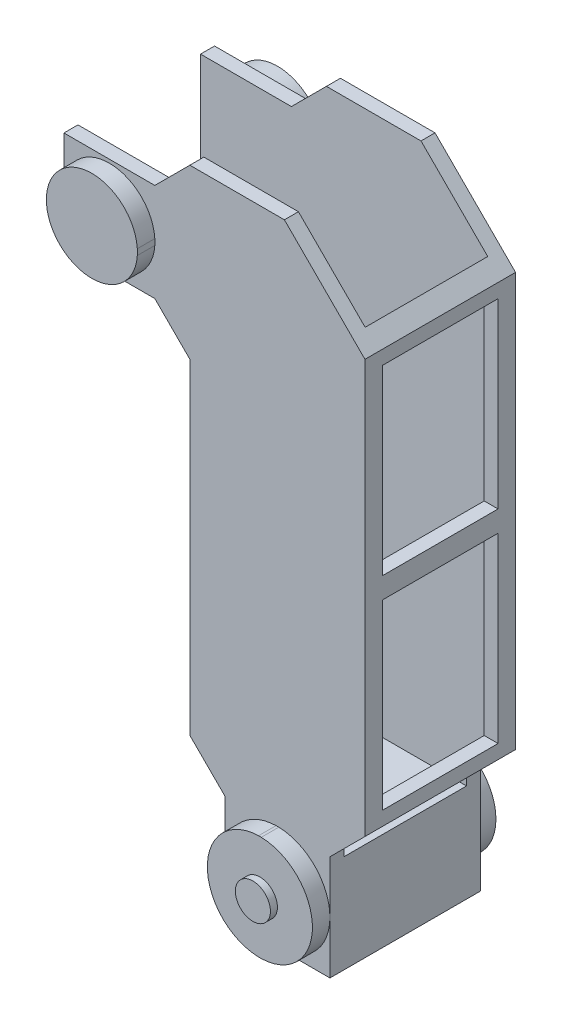
SolidWorks part; units mm, degrees
ref_plane "Front Plane" through (0, 0, 0) normal (0, 0, 1) x (1, 0, 0)
ref_plane "Top Plane" through (0, 0, 0) normal (0, 1, 0) x (1, 0, 0)
ref_plane "Right Plane" through (0, 0, 0) normal (1, 0, 0) x (0, 0, -1)
sketch "Sketch1" plane through (0, 0, 0) normal (0, 0, 1) x (1, 0, 0)
  line L0 (-42.9449, 80.5) -> (-16.9666, 80.5)
  line L1 (-7, 90.5) -> (20, 90.5)
  line L2 (-42.9449, 80.5) -> (-42.9449, 52.5)
  line L3 (3, -90.48) -> (33, -90.48)
  line L4 (43, 67.5) -> (43, -50.5)
  line L5 (-38.2486, 80.5) -> (43, -90.5) construction
  line L6 (-43, -90.5) -> (43, 90.5) construction
  line L7 (-7, 90.5) -> (-17, 80.5)
  line L8 (20, 90.5) -> (43, 67.5)
  line L11 (-7, 42.52) -> (-7, -50.48)
  line L14 (3, -90.48) -> (3, -60.48)
  line L15 (33, -90.48) -> (33, -60.5)
  line L17 (43, -50.5) -> (33, -60.5)
  line L18 (-7, -50.48) -> (3, -60.48)
  line L23 (-42.9449, 52.52) -> (-42.9449, 52.5)
  line L24 (-17, 52.52) -> (-42.9449, 52.52)
  line L26 (-7, 42.52) -> (-17, 52.52)
  circle A0 centre (17.8984, -75.5) radius 14.5
  circle A1 centre (-29.9725, 66.5) radius 13
  point P0 (0, 0)
  point P6 (-42.9449, 80.5)
  point P7 (-42.9449, 66.5)
  point P9 (43, 67.5)
  point P10 (20, 90.5)
  point P11 (-7, 90.5)
  point P14 (-17, 80.5)
  point P19 (-42.9449, 68.3358)
  point P25 (-7, -50.48)
  point P33 (43, -50.5)
  point P35 (3, -90.48)
  point P36 (33, -90.48)
  point P55 (-7, 42.52)
extrude "Boss-Extrude1" add sketch "Sketch1" along normal blind 43 contours A1 L2 L24 L26 L11 L18 L14 L3 L15 L17 L4 L8 L1 L7 L0 A0 region at (14.8624, 14.6618, 0)
extrude "Boss-Extrude2" add sketch "Sketch1<5>" along normal blind 43 contours A0 region at (17.8984, -75.5, 0)
sketch "Sketch1<5>" plane through (0, 0, 0) normal (0, 0, 1) x (1, 0, 0) same geometry as "Sketch1"
extrude "Boss-Extrude3" add sketch "Sketch1<6>" along normal blind 43 contours L2 A1 region at (-29.9717, 66.5, 0)
sketch "Sketch1<6>" plane through (0, 0, 0) normal (0, 0, 1) x (1, 0, 0) same geometry as "Sketch1"
extrude "Boss-Extrude4" add sketch "Sketch1<7>" against normal blind 5 contours L2 A1 region at (-29.9717, 66.5, 0)
sketch "Sketch1<7>" plane through (0, 0, 0) normal (0, 0, 1) x (1, 0, 0) same geometry as "Sketch1"
extrude "Boss-Extrude5" add sketch "Sketch1<8>" against normal blind 5 contours A0 region at (17.8984, -75.5, 0)
sketch "Sketch1<8>" plane through (0, 0, 0) normal (0, 0, 1) x (1, 0, 0) same geometry as "Sketch1"
sketch "Sketch3" plane through (0, 0, -5) normal (0, 0, -1) x (-1, 0, 0)
  circle A0 centre (-17.8984, -75.5) radius 5
  point P0 (-17.8984, -75.5)
extrude "Boss-Extrude6" add sketch "Sketch3" along normal blind 2
sketch "Sketch4" plane through (0, 0, 43) normal (0, 0, 1) x (1, 0, 0)
  line L0 (-17, 80.5) -> (-17, 52.52)
  line L1 (-17, 66.51) -> (-42.9449, 66.51)
  line L2 (-42.9449, 80.5) -> (-42.9449, 52.52) construction
  line L3 (3, -60.48) -> (33, -60.5)
  line L4 (18, -60.49) -> (18, -90.48)
  line L5 (3, -90.48) -> (33, -90.48) construction
  circle A0 centre (-29.9725, 66.51) radius 13
  circle A1 centre (18, -75.485) radius 15
  point P8 (-29.9725, 66.51)
  point P19 (18, -75.485)
  line M3 (-42.9449, 80.5) -> (-42.9449, 52.52)
  line M9 (3, -90.48) -> (33, -90.48)
extrude "Boss-Extrude7" add sketch "Sketch4" along normal blind 5 contours L0 A0 L1 M3 | A0 L0 L1 M3 region at (-29.9725, 72.028, 43) region at (-29.9725, 60.992, 43)
extrude "Boss-Extrude8" add sketch "Sketch4<3>" along normal blind 5 contours L3 A1 L4 M9 | A1 L3 L4 M9 region at (11.6338, -75.485, 43) region at (24.3662, -75.485, 43)
sketch "Sketch4<3>" plane through (0, 0, 43) normal (0, 0, 1) x (1, 0, 0) same geometry as "Sketch4"
sketch "Sketch5" plane through (0, 0, 48) normal (0, 0, 1) x (1, 0, 0)
  circle A0 centre (18, -75.485) radius 5
extrude "Boss-Extrude9" add sketch "Sketch5" along normal blind 2
sketch "Sketch6" plane through (-42.9449, 0, 0) normal (-1, 0, 0) x (0, 0, 1)
  line L0 (43, 80.5) -> (0, 80.5) construction
  line L1 (21.5, 80.5) -> (21.5, 52.52)
  line L2 (43, 52.52) -> (0, 52.52) construction
  line L4 (4, 80.51) -> (39, 80.51)
  line L5 (4, 80.51) -> (4, 52.51)
  line L6 (4, 52.51) -> (39, 52.51)
  line L7 (39, 80.51) -> (39, 52.51)
  line L8 (4, 80.51) -> (39, 52.51) construction
  line L9 (4, 52.51) -> (39, 80.51) construction
  point P0 (21.5, 80.5)
  point P7 (21.5, 66.51)
  line M8 (0, 52.52) -> (43, 52.52)
  line M14 (43, 80.5) -> (0, 80.5)
  dimension "D1" = 35
  dimension "D2" = 28
extrude "Cut-Extrude1" cut sketch "Sketch6" against normal blind 82 contours L5 L1 M14 M8 | L7 L1 M14 M8 region at (-42.9449, 66.51, 30.25) region at (-42.9449, 66.51, 12.75)
sketch "Sketch7" plane through (0, 90.5, 0) normal (0, 1, 0) x (1, 0, 0)
  line L0 (-7, -43) -> (20, -43) construction
  line L1 (-7, 0) -> (20, 0) construction
  line L2 (6.5, -43) -> (6.5, 0)
  line L4 (39.05, -39) -> (-26.05, -39)
  line L5 (39.05, -39) -> (39.05, -4)
  line L6 (39.05, -4) -> (-26.05, -4)
  line L7 (-26.05, -39) -> (-26.05, -4)
  line L8 (39.05, -39) -> (-26.05, -4) construction
  line L9 (39.05, -4) -> (-26.05, -39) construction
  point P0 (6.5, -43)
  point P1 (6.5, 0)
  point P8 (6.5, -21.5)
  line M4 (-7, 0) -> (-7, -43)
  line M6 (20, -43) -> (20, 0)
  dimension "D1" = 65.1
  dimension "D2" = 35
extrude "Cut-Extrude4" cut sketch "Sketch7" against normal blind 153 contours L7 L4 L6 M4 | L2 L6 L4 M4 | L6 L2 L4 M6 | L5 L6 L4 M6 region at (-0.25, 90.5, 21.5) region at (13.25, 90.5, 21.5) region at (29.525, 90.5, 21.5) region at (-16.525, 90.5, 21.5)
sketch "Sketch9" plane through (43, 0, 0) normal (1, 0, 0) x (0, 0, -1)
  line L0 (-43, 67.5) -> (0, 67.5) construction
  line L1 (-43, 67.5) -> (-43, -50.5) construction
  line L6 (-38, 63.5) -> (-5, 63.5)
  line L7 (-38, 63.5) -> (-38, 11.5)
  line L8 (-38, 11.5) -> (-5, 11.5)
  line L9 (-5, 63.5) -> (-5, 11.5)
  line L10 (-38, 63.5) -> (-5, 11.5) construction
  line L11 (-38, 11.5) -> (-5, 63.5) construction
  line L12 (-38, 5.5) -> (-5, 5.5)
  line L13 (-38, 5.5) -> (-38, -46.5)
  line L14 (-38, -46.5) -> (-5, -46.5)
  line L15 (-5, 5.5) -> (-5, -46.5)
  line L16 (-38, 5.5) -> (-5, -46.5) construction
  line L17 (-38, -46.5) -> (-5, 5.5) construction
  point P0 (-21.5, 67.5)
  point P1 (-43, 8.5)
  point P12 (-21.5, 37.5)
  point P13 (-21.5, -20.5)
  point P14 (-21.5, 37.5)
  point P19 (-21.5, -20.5)
  dimension "D3" = 52
  dimension "D4" = 33
  dimension "D5" = 33
  dimension "D6" = 52
extrude "Cut-Extrude5" cut sketch "Sketch9" against normal blind 33
ref_point "Point5"
ref_point "Point6"
ref_point "Point9"
ref_point "Point10"
ref_plane "Plane8" through (0, 66.5, 0) normal (0, 1, 0) x (1, 0, 0)
sketch "Sketch11" plane through (0, 66.5, 0) normal (0, 1, 0) x (1, 0, 0)
  line L0 (-29.9717, 5) -> (-29.9717, -47.7581)
  point P0 (-29.9717, -21.3791)
ref_point "Point13"
